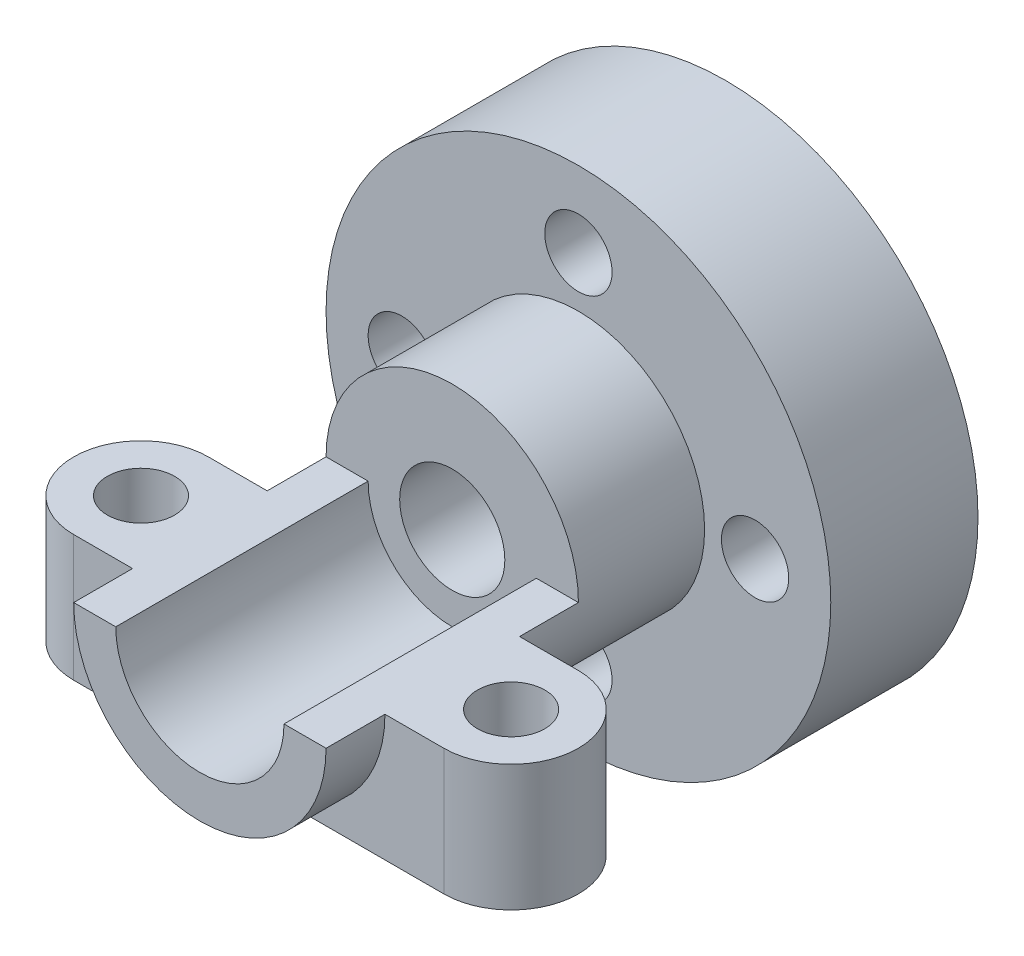
SolidWorks part; units mm, degrees
ref_plane "Front Plane" through (0, 0, 0) normal (0, 0, 1) x (1, 0, 0)
ref_plane "Top Plane" through (0, 0, 0) normal (0, 1, 0) x (1, 0, 0)
ref_plane "Right Plane" through (0, 0, 0) normal (1, 0, 0) x (0, 0, -1)
sketch "Sketch1" plane through (0, 0, 0) normal (0, 0, 1) x (1, 0, 0)
  line L0 (0, 0) -> (40446.7609, 0) construction
  line L1 (0, 0) -> (0, 40446.7609) construction
  line L2 (-20, 0) -> (-30, 0)
  line L3 (20, 0) -> (30, 0)
  circle A0 centre (0, 0) radius 12.5
  circle A1 centre (0, 0) radius 30
  circle A2 centre (0, 0) radius 42 construction
  circle A3 centre (0, 0) radius 60
  circle A4 centre (42, 0) radius 8
  circle A5 centre (0, -42) radius 8
  circle A6 centre (-42, 0) radius 8
  circle A7 centre (0, 42) radius 8
  arc A8 (20, 0) -> (-20, 0) centre (0, 0) cw
  point P21 (0, 0)
  dimension "D1" = 25
  dimension "D2" = 60
  dimension "D3" = 84
  dimension "D4" = 120
  dimension "D5" = 16
  dimension "D7" = 20
  dimension "D6" = 4
extrude "Boss-Extrude1" add sketch "Sketch1" along normal blind 125 contours L3 A8 L2 A1 region at (0, -20.6708, 0)
extrude "Boss-Extrude2" add sketch "Sketch1<3>" along normal blind 65 contours A8 L3 A1 L2 A0 region at (-25, 0.781, 0)
sketch "Sketch1<3>" plane through (0, 0, 0) normal (0, 0, 1) x (1, 0, 0) same geometry as "Sketch1"
extrude "Boss-Extrude3" add sketch "Sketch1<4>" along normal blind 35 contours A3 A7 A6 A5 A4 A1 region at (-58.3029, 0, 0)
sketch "Sketch1<4>" plane through (0, 0, 0) normal (0, 0, 1) x (1, 0, 0) same geometry as "Sketch1"
sketch "Sketch2" plane through (0, 0, 125) normal (0, 0, 1) x (1, 0, 0)
  line L0 (30, 0) -> (60, 0)
  line L1 (60, 0) -> (60, -30)
  line L2 (60, -30) -> (0, -30)
  circle A0 centre (0, 0) radius 30 construction
  circle A1 centre (0, 0) radius 30
  arc M7 (-30, 0) -> (30, 0) centre (0, 0) ccw
  dimension "D1" = 60
extrude "Boss-Extrude4" add sketch "Sketch2" against normal blind 32 from offset 14 contours L2 L1 L0 M7 region at (41.1658, -16.4663, 125) offset against normal yes
fillet "Fillet1" 2 edges at (60, -15, 111) (60, -15, 79) type full round first side face at (39.0533, -16.5533, 111) second side face at (39.0533, -16.5533, 79) middle face at (60, -15, 95)
hole_wizard "Ø16.0mm Dowel Hole1" positions "3DSketch1" profile "Sketch3" hole size "Ø16.0" standard "ISO" end condition through all
sketch3d "3DSketch1"
  line L0 (44, 0, 95) -> (44, -30, 95) construction
  point P0 (44, 0, 95)
sketch "Sketch3" plane through (44, 0, 95) normal (1, 0, 0) x (0, 0, 1)
  line L0 (0, 0) -> (0, 60)
  line L1 (0, 60) -> (8, 60)
  line L2 (8, 60) -> (8, 0)
  line L5 (8, 0) -> (0, 0)
  line L11 (0, -6.35) -> (0, 107.95) construction
  dimension "Thru Hole Dia." = 16
  dimension "Thru Hole Depth" = 60
mirror "Mirror1" about plane through (0, 0, 0) normal (1, 0, 0) of "Ø16.0mm Dowel Hole1", "Fillet1", "Boss-Extrude4"
sketch "Sketch4" plane through (0, 0, 0) normal (0, 0, -1) x (-1, 0, 0)
  circle A0 centre (0, 0) radius 55
  dimension "D1" = 110
extrude "Cut-Extrude1" cut sketch "Sketch4" against normal blind 15 contours A0
